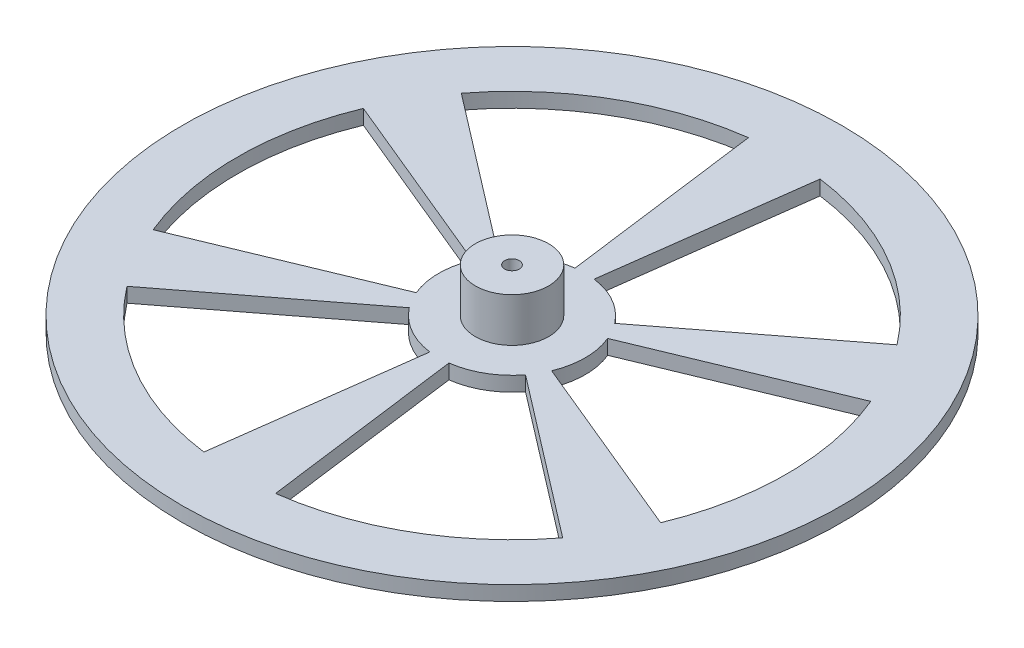
SolidWorks part; units mm, degrees
material "氧化铝"
ref_plane "前视基准面" through (0, 0, 0) normal (0, 0, 1) x (1, 0, 0)
ref_plane "上视基准面" through (0, 0, 0) normal (0, 1, 0) x (1, 0, 0)
ref_plane "右视基准面" through (0, 0, 0) normal (1, 0, 0) x (0, 0, -1)
other "Configuration Table"
sketch "草图1" plane through (0, 0, 0) normal (0, 1, 0) x (1, 0, 0)
  circle A0 centre (0, 0) radius 90
  dimension "D1" = 180
extrude "凸台-拉伸1" add sketch "草图1" along normal blind 4
sketch "草图2" plane through (0, 4, 0) normal (0, 1, 0) x (1, 0, 0)
  line L0 (0, 20) -> (0, 75)
  line L1 (-17.3205, 10) -> (-64.9519, 37.5)
  line L2 (-2.6105, 19.8289) -> (-9.7895, 74.3584)
  line L3 (-15.8671, 12.1752) -> (-59.5015, 45.6571)
  circle A0 centre (0, 0) radius 20
  circle A1 centre (0, 0) radius 75
  dimension "D1" = 40
  dimension "D2" = 60
  dimension "D3" = 7.5
  dimension "D4" = 7.5
ref_axis "基准轴1" through (0, 4, 0) along (0, 1, 0)
extrude "切除-拉伸1" cut sketch "草图2" against normal through all contours L2 A1 L3 A0 region at (-25.7301, 4, -44.5658)
pattern_circular "阵列(圆周)1" count 6 over 360 about axis through (0, 4, 0) along (0, 1, 0) of "切除-拉伸1"
sketch "草图6" plane through (0, 4, 0) normal (0, 1, 0) x (1, 0, 0)
  circle A0 centre (0, 0) radius 10
extrude "凸台-拉伸2" add sketch "草图6" along normal blind 12
sketch "草图7" plane through (0, 16, 0) normal (0, 1, 0) x (1, 0, 0)
  circle A0 centre (0, 0) radius 2
extrude "切除-拉伸2" cut sketch "草图7" against normal blind 12
sketch "草图8" plane through (0, 0, 0) normal (0, -1, 0) x (1, 0, 0)
  point P0 (0, 0)
